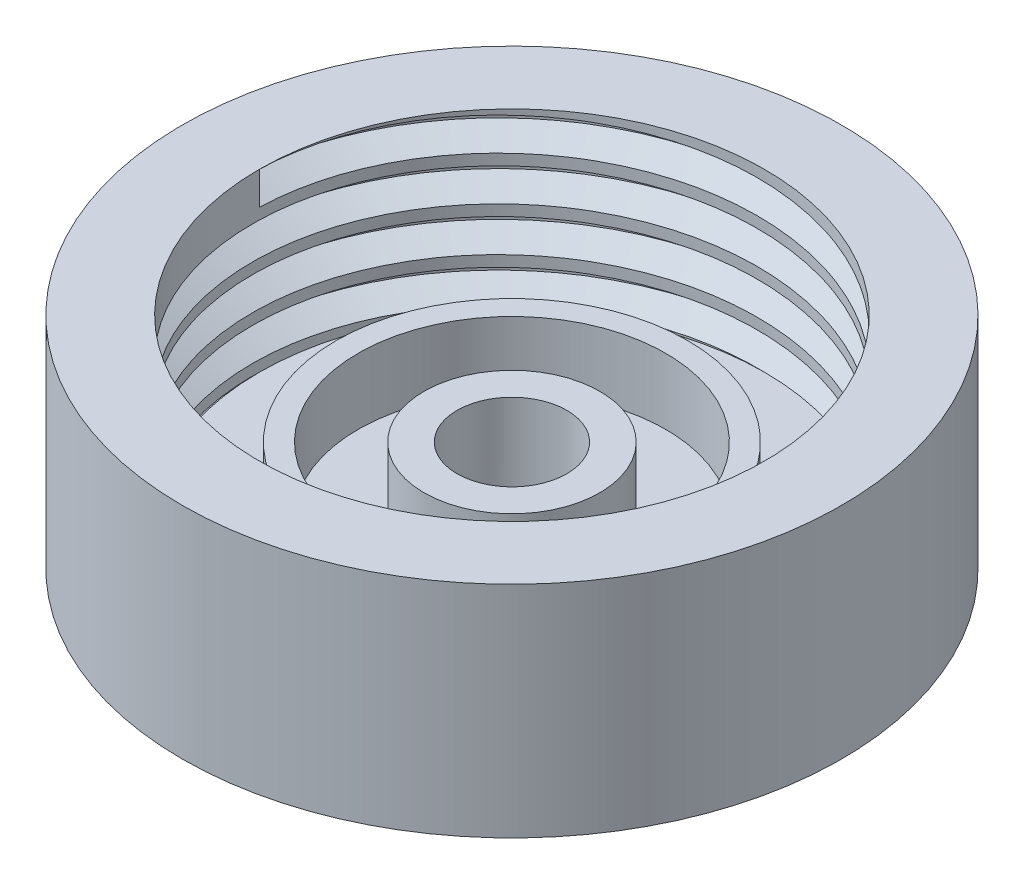
SolidWorks part; units mm, degrees
material "PVC 0.007 Plasticized"
ref_plane "Front Plane" through (0, 0, 0) normal (0, 0, 1) x (1, 0, 0)
ref_plane "Top Plane" through (0, 0, 0) normal (0, 1, 0) x (1, 0, 0)
ref_plane "Right Plane" through (0, 0, 0) normal (1, 0, 0) x (0, 0, -1)
sketch "Sketch1" plane through (0, 0, 0) normal (0, 1, 0) x (1, 0, 0)
  circle A0 centre (0, 0) radius 15
  dimension "D1" = 30
extrude "Boss-Extrude1" add sketch "Sketch1" along normal blind 2
sketch "Sketch2" plane through (0, 2, 0) normal (0, 1, 0) x (1, 0, 0)
  circle A0 centre (0, 0) radius 11.5
  circle A1 centre (0, 0) radius 15
  circle A2 centre (0, 0) radius 15
  dimension "D2" = 23
  dimension "D1" = 0
extrude "Boss-Extrude2" add sketch "Sketch2" along normal blind 8
sketch "Sketch3" plane through (0, 2, 0) normal (0, 1, 0) x (1, 0, 0)
  circle A0 centre (0, 0) radius 8
  circle A1 centre (0, 0) radius 7
  circle A2 centre (0, 0) radius 4
  circle A3 centre (0, 0) radius 2.5
  dimension "D1" = 16
  dimension "D2" = 14
  dimension "D3" = 8
  dimension "D4" = 5
extrude "Boss-Extrude3" add sketch "Sketch3" along normal blind 3 contours A0 | A1 | A2 | A3
thread "Thread2" pitch 2 method cut profile "Thread Profile2" start angle 0, offset 0, length 8, pitch 2, diameter 23
ref_plane "Plane2" through (-11.5, 10, 0) normal (0, 0, 1) x (-1, 0, 0)
sketch "Thread Profile2" plane through (-11.5, 10, 0) normal (0, 0, 1) x (-1, 0, 0)
  line L0 (0, 0) -> (0, 2) construction
  line L1 (0, 0) -> (1.0825, 0.625)
  line L2 (1.0825, 0.625) -> (1.0825, 0.875)
  line L3 (1.0825, 0.875) -> (0, 1.5)
  line L4 (1.0825, 0.75) -> (0, 0.75) construction
  line L11 (0, 0) -> (0, 1.5)
  point P2 (0, 0)
  dimension "Pitch" = 2
  dimension "Profile_Angle" = 60
  dimension "Profile_Land" = 0.25
  dimension "Profile_Height" = 1.0825
sketch "Sketch10" plane through (0, 2, 0) normal (0, 1, 0) x (1, 0, 0)
  circle A1 centre (0, 0) radius 2.5
  circle A2 centre (0, 0) radius 2.5
  dimension "D1" = 0
extrude "Cut-Extrude1" cut sketch "Sketch10" against normal blind 5
sketch "Sketch11" plane through (0, 0, 0) normal (0, -1, 0) x (1, 0, 0)
  circle A0 centre (0, 0) radius 10
  circle A1 centre (0, 0) radius 15 construction
  circle A2 centre (0, 0) radius 2.5 construction
  circle A3 centre (0, 0) radius 2.5
  dimension "D1" = 20
extrude "Boss-Extrude4" add sketch "Sketch11" along normal blind 0.5
